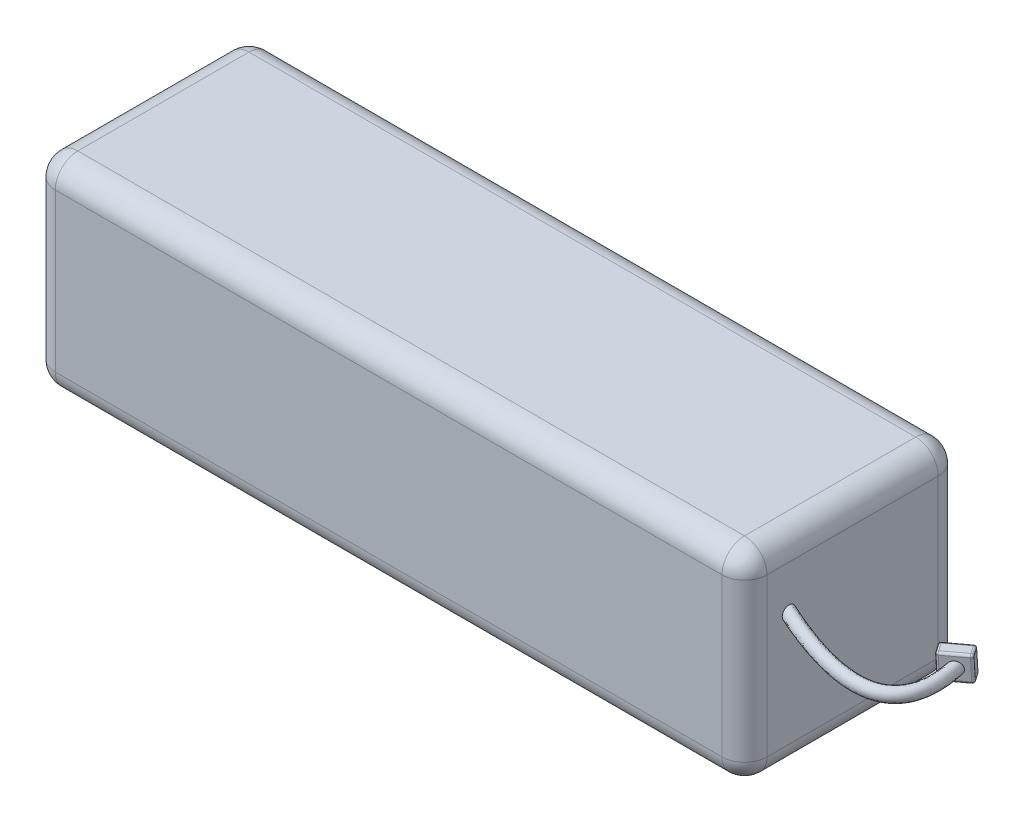
SolidWorks part; units mm, degrees
ref_plane "Front Plane" through (0, 0, 0) normal (0, 0, 1) x (1, 0, 0)
ref_plane "Top Plane" through (0, 0, 0) normal (0, 1, 0) x (1, 0, 0)
ref_plane "Right Plane" through (0, 0, 0) normal (1, 0, 0) x (0, 0, -1)
sketch "Sketch1" plane through (0, 0, 0) normal (0, 0, 1) x (1, 0, 0)
  line L1 (-79, -22.5) -> (79, -22.5)
  line L2 (-79, -22.5) -> (-79, 22.5)
  line L3 (-79, 22.5) -> (79, 22.5)
  line L4 (79, -22.5) -> (79, 22.5)
  line L5 (-79, -22.5) -> (79, 22.5) construction
  line L6 (-79, 22.5) -> (79, -22.5) construction
  point P0 (0, 0)
  dimension "D1" = 45
  dimension "D2" = 158
extrude "Boss-Extrude1" add sketch "Sketch1" along normal blind 48
fillet "Fillet1" radius 5 12 edges at (79, 0, 48) (79, 22.5, 24) (79, 0, 0) (-79, 0, 0) (-79, 22.5, 24) (-79, -22.5, 24) (-79, 0, 48) (79, -22.5, 24) (0, -22.5, 48) (0, -22.5, 0) (0, 22.5, 0) (0, 22.5, 48)
sketch "Sketch3" plane through (79, 0, 0) normal (1, 0, 0) x (0, 0, -1)
  circle A0 centre (-38.1222, 7.7831) radius 1.5
  dimension "D1" = 3
sketch3d "3DSketch3"
  spline S0 degree 2 poles (79, 7.7831, 38.1222) (111.751, 6.7976, 52.4509) (107.6541, 7.2712, 29.9275) knots 0 0 0 1 1 1
sweep "Sweep2" add profiles "Sketch3" path "3DSketch3"
sketch "Sketch4" plane through (47.1183, -4.1699, 69.996) normal (-0.5577, 0.0494, -0.8285) x (-0.83, -0.0356, 0.5566)
  line L1 (-76.0336, 11.7501) -> (-69.8773, 11.7501)
  line L2 (-76.0336, 11.7501) -> (-76.0336, 5.9662)
  line L3 (-76.0336, 5.9662) -> (-69.8773, 5.9662)
  line L4 (-69.8773, 11.7501) -> (-69.8773, 5.9662)
  line L5 (-76.0336, 11.7501) -> (-69.8773, 5.9662) construction
  line L6 (-76.0336, 5.9662) -> (-69.8773, 11.7501) construction
  point P0 (-72.9554, 8.8581)
extrude "Boss-Extrude2" add sketch "Sketch4" along normal blind 3
fillet "Fillet2" radius 0.5 12 edges at (107.66, 4.3846, 29.7515) (104.2685, 4.349, 30.222) (105.0992, 7.1616, 31.6408) (103.426, 7.3096, 29.1551) (104.2567, 10.1222, 30.5739) (105.9749, 10.3059, 27.6178) (107.6482, 10.1578, 30.1034) (110.209, 7.3809, 28.2142) (108.5357, 7.529, 25.7285) (105.9868, 4.5327, 27.2659) (109.3783, 4.5683, 26.7954) (109.3664, 10.3416, 27.1473)
